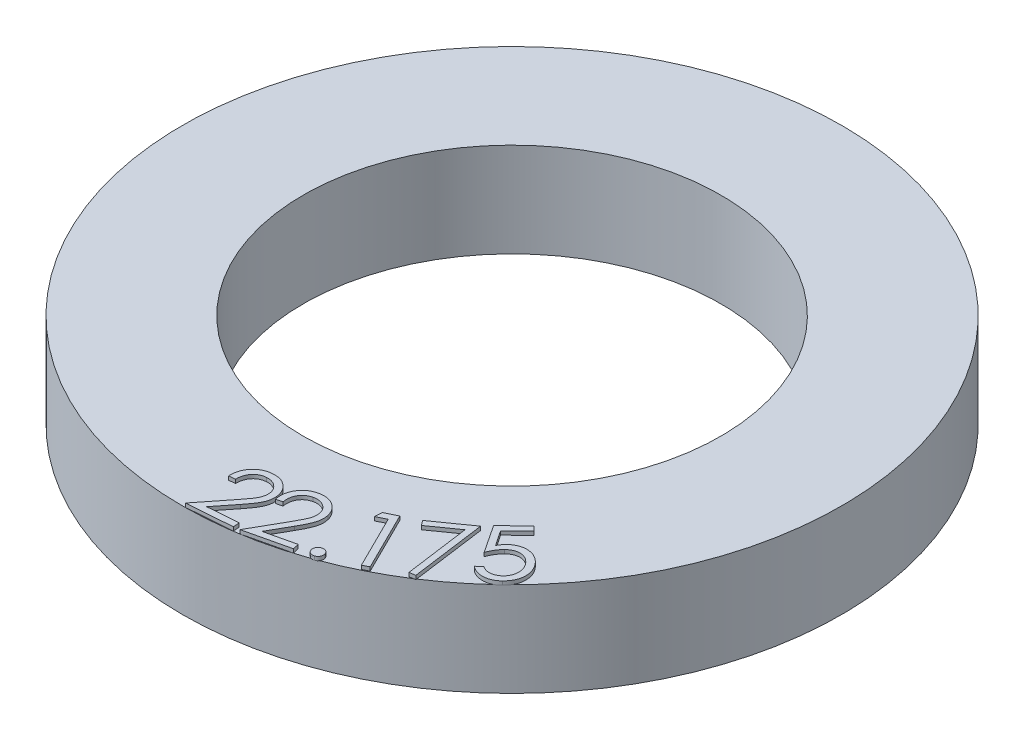
SolidWorks part; units mm, degrees
ref_plane "Front Plane" through (0, 0, 0) normal (0, 0, 1) x (1, 0, 0)
ref_plane "Top Plane" through (0, 0, 0) normal (0, 1, 0) x (1, 0, 0)
ref_plane "Right Plane" through (0, 0, 0) normal (1, 0, 0) x (0, 0, -1)
ref_axis "X" through (-88.99, 0, 0) along (1, 0, 0)
ref_axis "Y" through (0, 55, 0) along (0, -1, 0)
ref_axis "Z" through (0, 0, -88.99) along (0, 0, 1)
sketch "Sketch1" plane through (0, 0, 0) normal (0, 1, 0) x (1, 0, 0)
  circle A0 centre (0, 0) radius 17.5
  circle A1 centre (0, 0) radius 11.0875
  dimension "D1" = 35
  dimension "D2" = 22.175
extrude "Boss-Extrude1" add sketch "Sketch1" along normal blind 5
sketch "Sketch7" plane through (0, 5, 0) normal (0, 1, 0) x (1, 0, 0)
  text T0 "22.175"
extrude "Boss-Extrude7" add sketch "Sketch7" along normal blind 0.2
